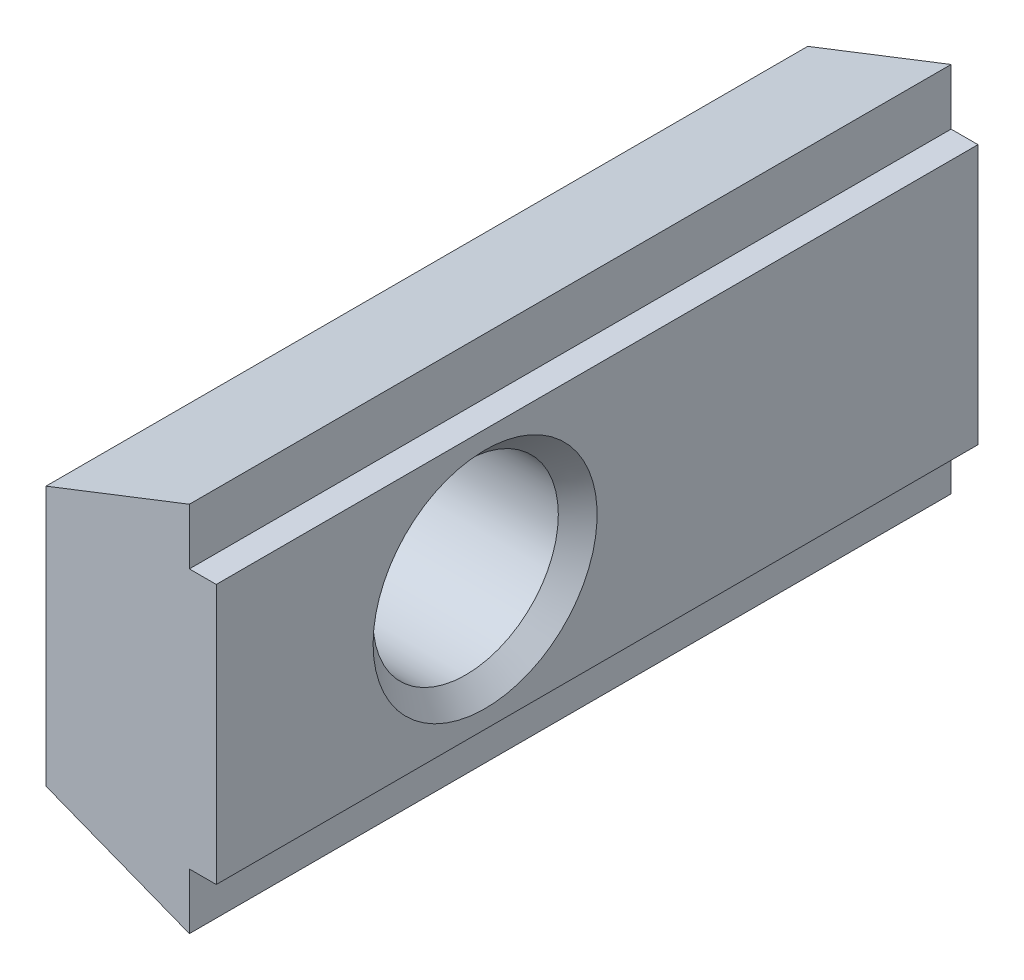
SolidWorks part; units mm, degrees
ref_plane "正面" through (0, 0, 0) normal (0, 0, 1) x (1, 0, 0)
ref_plane "平面" through (0, 0, 0) normal (0, 1, 0) x (1, 0, 0)
ref_plane "右側面" through (0, 0, 0) normal (1, 0, 0) x (0, 0, -1)
ref_plane "平面1" through (0, 0, 0) normal (0, 0, 1) x (1, 0, 0)
sketch "ｽｹｯﾁ1" plane through (0, 0, 0) normal (0, 0, 1) x (1, 0, 0)
  line L0 (0, -2.9) -> (3.2, -4.15)
  line L1 (3.2, -4.15) -> (3.2, -2.9)
  line L2 (3.2, -2.9) -> (3.8, -2.9)
  line L3 (3.8, -2.9) -> (3.8, 2.9)
  line L4 (3.8, 2.9) -> (3.2, 2.9)
  line L5 (3.2, 2.9) -> (3.2, 4.15)
  line L6 (3.2, 4.15) -> (0, 2.9)
  line L7 (0, 2.9) -> (0, -2.9)
extrude "ﾎﾞｽ - 押し出し1" add sketch "ｽｹｯﾁ1" against normal blind 8.5 and the other way blind 8.5
ref_plane "平面2" through (0, 0, 2.5) normal (0, 0, 1) x (1, 0, 0)
sketch "ｽｹｯﾁ2" plane through (0, 0, 2.5) normal (0, 0, 1) x (1, 0, 0)
  line L0 (0, 0) -> (0, 2.5)
  line L1 (0, 2.5) -> (0.433, 2.067)
  line L2 (0.433, 2.067) -> (3.367, 2.067)
  line L3 (3.367, 2.067) -> (3.8, 2.5)
  line L4 (3.8, 2.5) -> (3.8, 0)
  line L5 (3.8, 0) -> (0, 0)
  line L6 (3.8, 0) -> (0, 0) construction
revolve "ｶｯﾄ - 回転1" cut sketch "ｽｹｯﾁ2" angle 360 about L6 reverse direction yes
ref_plane "平面3" through (0, 0, -4.25) normal (0, 0, 1) x (1, 0, 0)
sketch "ｽｹｯﾁ3" plane through (0, 0, -4.25) normal (0, 0, 1) x (1, 0, 0)
  line L0 (1.2, 2) -> (1.2, -2)
  line L1 (1.2, 3.2) -> (1.2, -3.2) construction
  arc A0 (1.2, -2) -> (1.2, 2) centre (1.2, 0) cw
revolve "回転1" add sketch "ｽｹｯﾁ3" angle 360 about L1 reverse direction yes
